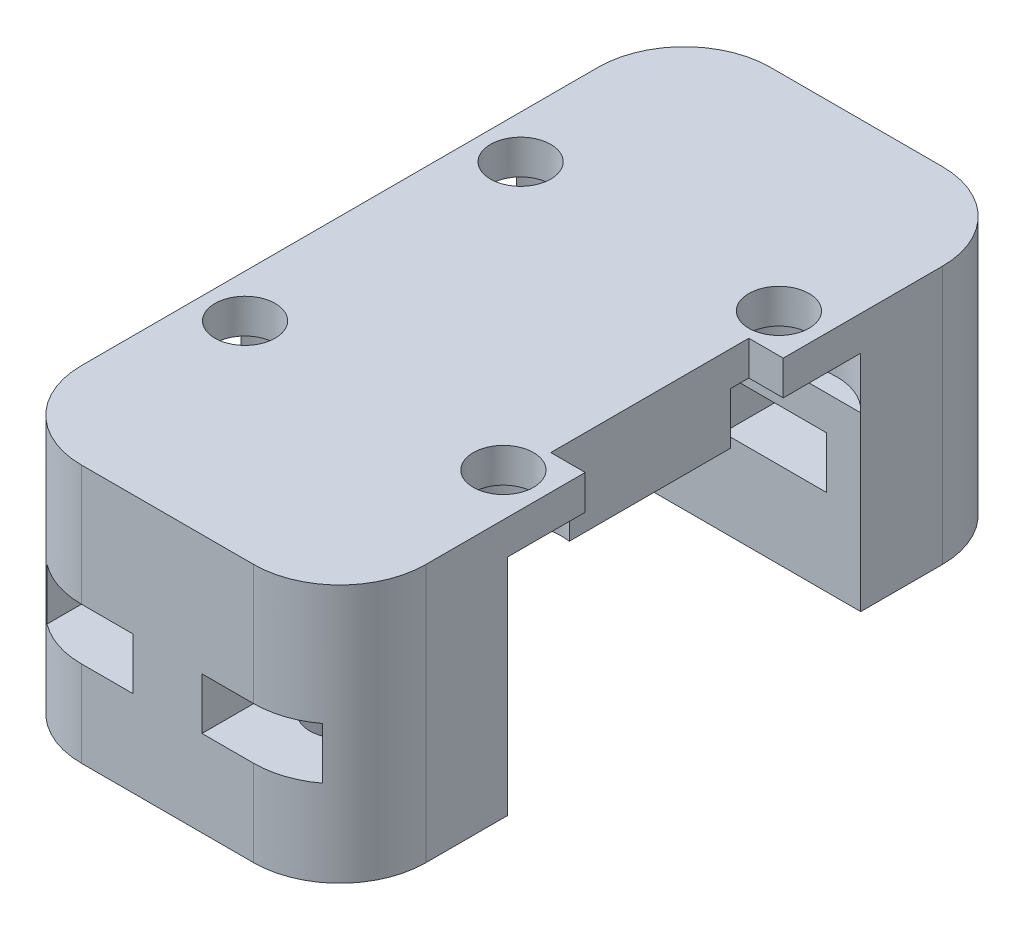
SolidWorks part; units mm, degrees
material "ABS"
ref_plane "Front Plane" through (0, 0, 0) normal (0, 0, 1) x (1, 0, 0)
ref_plane "Top Plane" through (0, 0, 0) normal (0, 1, 0) x (1, 0, 0)
ref_plane "Right Plane" through (0, 0, 0) normal (1, 0, 0) x (0, 0, -1)
sketch "Sketch1" plane through (0, 0, 0) normal (0, 1, 0) x (1, 0, 0)
  line L1 (-10, -20) -> (10, -20)
  line L2 (-10, -20) -> (-10, 20)
  line L3 (-10, 20) -> (10, 20)
  line L4 (10, -20) -> (10, 20)
  line L5 (-10, -20) -> (10, 20) construction
  line L6 (-10, 20) -> (10, -20) construction
  point P0 (0, 0)
  dimension "D1" = 40
  dimension "D2" = 20
extrude "Boss-Extrude1" add sketch "Sketch1" along normal blind 5
sketch "Sketch2" plane through (0, 0, 0) normal (0, -1, 0) x (1, 0, 0)
  line L0 (10, 20) -> (10, -20) construction
  line L1 (-10, 20) -> (10, 20)
  line L2 (-10, 20) -> (-10, 10.25)
  line L3 (-10, 10.25) -> (10, 10.25)
  line L4 (10, 20) -> (10, 10.25)
  line L5 (-10, -20) -> (-10, 20) construction
  line L6 (10, -20) -> (-10, -20)
  line L7 (10, -20) -> (10, -10.25)
  line L8 (10, -10.25) -> (-10, -10.25)
  line L9 (-10, -20) -> (-10, -10.25)
  dimension "D1" = 9.75
  dimension "D2" = 9.75
extrude "Boss-Extrude2" add sketch "Sketch2" along normal blind 10
sketch "Sketch3" plane through (0, 5, 0) normal (0, 1, 0) x (1, 0, 0)
  line L0 (-10, -20) -> (10, -20) construction
  line L1 (-10, 20) -> (-10, -20) construction
  circle A0 centre (-7.5, -8) radius 1.75
  circle A1 centre (-7.5, 8) radius 1.75
  circle A2 centre (7.5, -8) radius 1.75
  circle A3 centre (7.5, 8) radius 1.75
  dimension "D1" = 3.5
  dimension "D4" = 3.5
  dimension "D6" = 3.5
  dimension "D8" = 3.5
  dimension "D2" = 12
  dimension "D3" = 2.5
  dimension "D5" = 16
  dimension "D7" = 15
extrude "Cut-Extrude1" cut sketch "Sketch3" against normal blind 5
sketch "Sketch4" plane through (0, 0, 0) normal (0, -1, 0) x (1, 0, 0)
  circle A13 centre (7.5, 8) radius 3.3634
  circle A14 centre (-7.5, 8) radius 3.3634
  circle A15 centre (-7.5, -8) radius 3.3634
  circle A16 centre (7.5, -8) radius 3.3634
extrude "Cut-Extrude2" cut sketch "Sketch4" against normal blind 3
sketch "Sketch5" plane through (0, -10, 0) normal (0, -1, 0) x (1, 0, 0)
  line L0 (10, -10.25) -> (-10, -10.25) construction
  line L1 (10, -20) -> (10, -10.25) construction
  line L2 (-10, 10.25) -> (10, 10.25) construction
  circle A0 centre (-5, -15) radius 1.75
  circle A1 centre (5, -15) radius 1.75
  circle A2 centre (-5, 15) radius 1.75
  circle A3 centre (5, 15) radius 1.75
  dimension "D1" = 3.5
  dimension "D3" = 3.5
  dimension "D6" = 3.5
  dimension "D7" = 4.75
  dimension "D8" = 3.5
  dimension "D2" = 4.75
  dimension "D4" = 10
  dimension "D5" = 5
extrude "Cut-Extrude3" cut sketch "Sketch5" against normal blind 8
sketch "Sketch6" plane through (0, -2, 0) normal (0, -1, 0) x (1, 0, 0)
  line L13 (-8, -20) -> (-2, -20)
  line L14 (-8, -20) -> (-8, -10)
  line L15 (-8, -10) -> (-2, -10)
  line L16 (-2, -20) -> (-2, -10)
  line L17 (-8, -20) -> (-2, -10) construction
  line L18 (-8, -10) -> (-2, -20) construction
  line L19 (8, -20) -> (2, -20)
  line L20 (8, -20) -> (8, -10)
  line L21 (8, -10) -> (2, -10)
  line L22 (2, -20) -> (2, -10)
  line L23 (8, -20) -> (2, -10) construction
  line L24 (8, -10) -> (2, -20) construction
  line L25 (8, 10) -> (2, 10)
  line L26 (8, 10) -> (8, 20)
  line L27 (8, 20) -> (2, 20)
  line L28 (2, 10) -> (2, 20)
  line L29 (8, 10) -> (2, 20) construction
  line L30 (8, 20) -> (2, 10) construction
  line L35 (-8, 20) -> (-2, 20)
  line L36 (-8, 20) -> (-8, 10)
  line L37 (-8, 10) -> (-2, 10)
  line L38 (-2, 20) -> (-2, 10)
  line L39 (-8, 20) -> (-2, 10) construction
  line L40 (-8, 10) -> (-2, 20) construction
  point P0 (-5, -15)
  point P7 (5, -15)
  point P13 (5, 15)
  point P18 (-5, 15)
  dimension "D1" = 6
  dimension "D2" = 10
  dimension "D3" = 6
  dimension "D4" = 10
  dimension "D6" = 10
extrude "Cut-Extrude4" cut sketch "Sketch6" along normal blind 3
sketch "Sketch7" plane through (0, -2, 0) normal (0, -1, 0) x (1, 0, 0)
  circle A0 centre (-5, -15) radius 1.75
  circle A1 centre (5, -15) radius 1.75
  circle A2 centre (5, 15) radius 1.75
  circle A3 centre (-5, 15) radius 1.75
  dimension "D1" = 3.5
  dimension "D2" = 3.5
  dimension "D3" = 3.5
  dimension "D4" = 3.5
extrude "Cut-Extrude5" cut sketch "Sketch7" against normal blind 3
fillet "Fillet1" radius 5 4 edges at (-10, -2.5, -20) (10, -2.5, -20) (-10, -2.5, 20) (10, -2.5, 20)
sketch "Sketch10" plane through (10, 0, 0) normal (1, 0, 0) x (0, 0, -1)
  line L0 (-15, 5) -> (15, 5) construction
  line L1 (-5.75, 0) -> (5.75, 0)
  line L2 (-5.75, 0) -> (-5.75, 5)
  line L3 (-5.75, 5) -> (5.75, 5)
  line L4 (5.75, 0) -> (5.75, 5)
  line L5 (5.75, 0) -> (5.75, 3) construction
extrude "Cut-Extrude6" cut sketch "Sketch10" against normal blind 2
